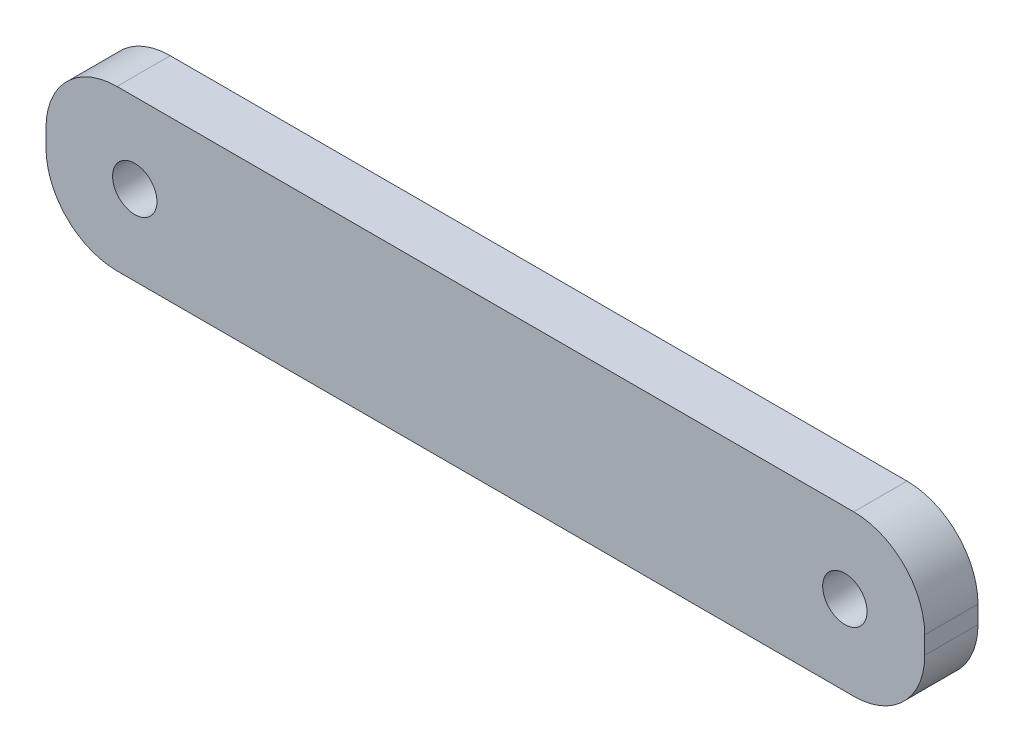
SolidWorks part; units mm, degrees
note: The reader was unsure of these and kept them because the rebuilt part matched: thickness of "Brida base1", "Chapa metálica4", "Chapa metálica5".
material "aluminio"
ref_plane "Alzado" through (0, 0, 0) normal (0, 0, 1) x (1, 0, 0)
ref_plane "Planta" through (0, 0, 0) normal (0, 1, 0) x (1, 0, 0)
ref_plane "Vista lateral" through (0, 0, 0) normal (1, 0, 0) x (0, 0, -1)
sketch "Croquis1" plane through (0, 0, 0) normal (0, 0, 1) x (1, 0, 0)
  line L0 (0, 4.5) -> (49.5, 4.5) construction
  line L1 (0, 0) -> (49.5, 0)
  line L2 (0, 0) -> (0, 9)
  line L3 (0, 9) -> (49.5, 9)
  line L4 (49.5, 0) -> (49.5, 9)
  circle A0 centre (5, 4.5) radius 1.25
  circle A1 centre (25, 4.5) radius 1.25 construction
  circle A2 centre (45, 4.5) radius 1.25
  dimension "D2" = 20
  dimension "D3" = 4.5
  dimension "D4" = 5
  dimension "D6" = 2.5
  dimension "D1" = 20
  dimension "D5" = 9
base flange "Brida base1" sketch "Croquis1" thickness 3 reverse thickness direction no parameters "D1"=0.7366
cosmetic thread "Rosca de taladro1"
cosmetic thread "Rosca de taladro3"
cosmetic thread "Rosca de taladro4"
cosmetic thread "Rosca de taladro5"
hole_wizard "Taladro roscado M31" positions "Croquis3D1" profile "Croquis6" tap size "M3" standard "Iso" end condition up to next
sketch3d "Croquis3D1"
  line L0 (5, 4.5, -3) -> (5, 4.5, 0) construction
  line L2 (45, 4.5, -3) -> (45, 4.5, 0) construction
  point P0 (5, 4.5, 0)
  point P8 (45, 4.5, 0)
sketch "Croquis6" plane through (5, 4.5, 0) normal (1, 0, 0) x (0, -1, 0)
  line L0 (0, 0) -> (0, 3)
  line L1 (0, 3) -> (1.25, 3)
  line L2 (1.25, 3) -> (1.25, 0)
  line L5 (1.25, 0) -> (0, 0)
  line L11 (0, -6.35) -> (0, 107.95) construction
  dimension "Diámetro de perforador para roscar hasta el siguiente" = 2.5
  dimension "Profundidad de perforador para roscar hasta el siguiente" = 3
fillet "Redondeo1" radius 4 4 edges at (49.5, 9, -1.5) (49.5, 0, -1.5) (0, 0, -1.5) (0, 9, -1.5)
sketch "Líneas de pliegue1" plane through (0, 0, 0) normal (0, 1, 0) x (1, 0, 0)
sketch "Cuadro delimitador1" plane through (0, 0, 0) normal (0, 1, 0) x (1, 0, 0)
sheet metal parameters "Chapa metálica4" thickness 3 parameters "D1"=0.7366
flat pattern "Chapa desplegada4" [suppressed]
sketch "Líneas de pliegue2" plane through (0, 0, 0) normal (0, 1, 0) x (1, 0, 0)
sketch "Cuadro delimitador2" [suppressed] plane through (0, 0, 0) normal (0, 1, 0) x (1, 0, 0)
sheet metal parameters "Chapa metálica5" thickness 3 parameters "D1"=0.7366, "D7"=2
flat pattern "Chapa desplegada4"
sketch "Líneas de pliegue2" plane through (0, 0, 0) normal (0, 1, 0) x (1, 0, 0)
sketch3d "Cuadro delimitador2" [suppressed]
  line L0 (0, 9, 0) -> (49.5, 9, 0) construction
  line L1 (0, 0, 0) -> (49.5, 0, 0) construction
  line L2 (0, 9, 0) -> (0, 0, 0) construction
  line L3 (49.5, 9, 0) -> (49.5, 0, 0) construction
